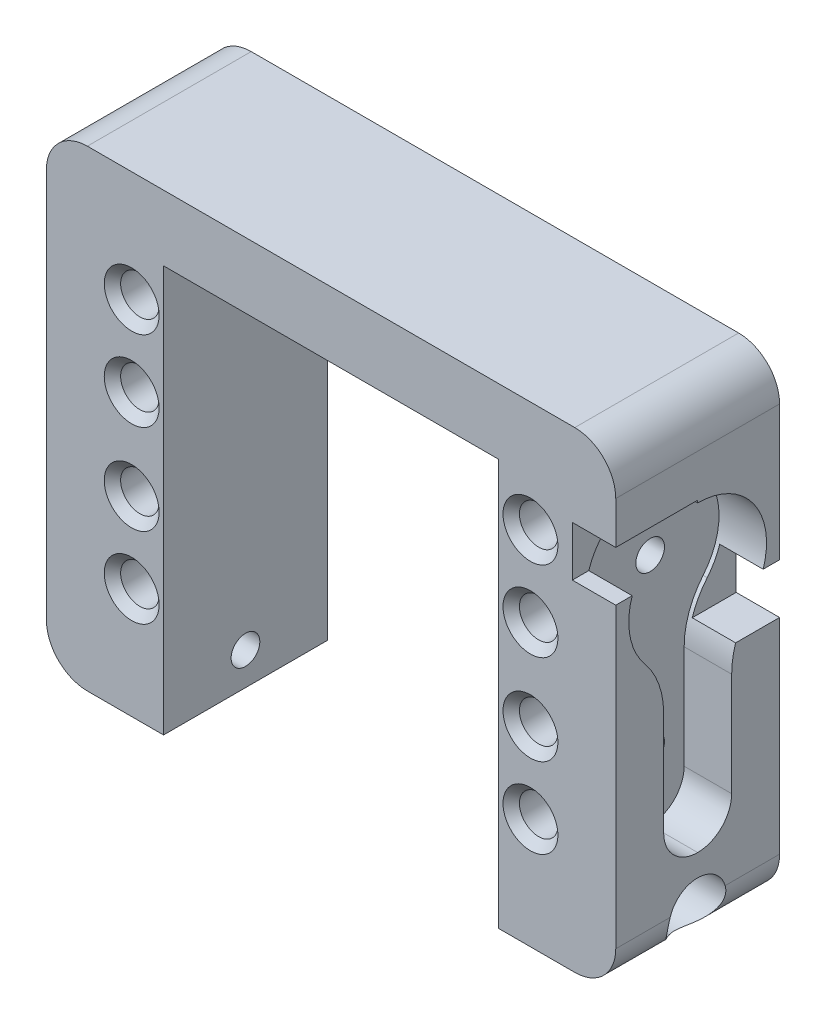
SolidWorks part; units mm, degrees
material "ABS"
ref_plane "Front Plane" through (0, 0, 0) normal (0, 0, 1) x (1, 0, 0)
ref_plane "Top Plane" through (0, 0, 0) normal (0, 1, 0) x (1, 0, 0)
ref_plane "Right Plane" through (0, 0, 0) normal (1, 0, 0) x (0, 0, -1)
sketch "Sketch1" plane through (0, 0, 0) normal (1, 0, 0) x (0, 0, -1)
  line L1 (-10, 10) -> (10, 10)
  line L2 (-10, 10) -> (-10, -10)
  line L3 (-10, -10) -> (10, -10)
  line L4 (10, 10) -> (10, -10)
  line L5 (-10, 10) -> (10, -10) construction
  line L6 (-10, -10) -> (10, 10) construction
  point P0 (0, 0)
  dimension "D1" = 20
  dimension "D2" = 20
extrude "Boss-Extrude1" add sketch "Sketch1" along normal blind 20
sketch "Sketch2" plane through (20, 0, 0) normal (1, 0, 0) x (0, 0, -1)
  line L1 (-10, 35) -> (10, 35)
  line L2 (-10, 35) -> (-10, -35)
  line L3 (-10, -35) -> (10, -35)
  line L4 (10, 35) -> (10, -35)
  line L5 (-10, 35) -> (10, -35) construction
  line L6 (-10, -35) -> (10, 35) construction
  point P0 (0, 0)
  dimension "D1" = 20
  dimension "D2" = 70
extrude "Boss-Extrude2" add sketch "Sketch2" along normal blind 10.3
sketch "Sketch4" plane through (30.3, 0, 0) normal (1, 0, 0) x (0, 0, -1)
  line L0 (0, 7.65) -> (0, 8.1702) construction
  line L1 (7.65, 7.65) -> (-7.65, 7.65) construction
  line L17 (4.15, -26.55) -> (-4.15, -26.55) construction
  line L18 (-7.65, 7.65) -> (7.65, 7.65) construction
  line L22 (-7.65, 7.65) -> (-7.65, -27.55) construction
  line L23 (-7.65, -27.55) -> (7.65, -27.55) construction
  line L24 (7.65, 7.65) -> (7.65, -27.55) construction
  line L25 (-7.65, 7.65) -> (7.65, -27.55) construction
  line L26 (-7.65, -27.55) -> (7.65, 7.65) construction
  line L27 (4.15, -26.55) -> (4.15, -28.55) construction
  line L28 (4.15, -28.55) -> (-4.15, -28.55) construction
  line L29 (-4.15, -26.55) -> (-4.15, -28.55) construction
  line L30 (4.15, -26.55) -> (-4.15, -28.55) construction
  line L31 (4.15, -28.55) -> (-4.15, -26.55) construction
  line L34 (4.15, -28.55) -> (-4.15, -28.55)
  line L35 (-4.15, -28.55) -> (-4.15, -7.3118)
  line L36 (4.15, -28.55) -> (4.15, -7.3118)
  arc A1 (4.15, -6.4265) -> (-4.15, -6.4265) centre (0, 0) ccw construction
  arc A2 (4.15, -7.3118) -> (-4.15, -7.3118) centre (0, 0) ccw
  point P1 (0, -27.55)
  point P7 (0, -13.75)
  point P10 (0, 7.65)
  point P14 (0, -9.95)
  dimension "D1" = 15.3
  dimension "D5" = 2
  dimension "D2" = 15.3
  dimension "D3" = 35.2
  dimension "D4" = 8.3
extrude "Cut-Extrude1" cut sketch "Sketch4" against normal blind 5.8
fillet "Fillet1" radius 4.15 2 edges at (27.4, -28.55, 4.15) (27.4, -28.55, -4.15)
fillet "Fillet2" radius 10 2 edges at (27.4, -7.3118, 4.15) (27.4, -7.3118, -4.15)
sketch "Sketch5" plane through (0, 0, 0) normal (-1, 0, 0) x (0, 0, 1)
  circle A0 centre (0, 0) radius 1.75
  dimension "D1" = 3.5
extrude "Cut-Extrude2" cut sketch "Sketch5" against normal through all
sketch "Sketch6" plane through (24.5, 0, 0) normal (1, 0, 0) x (0, 0, -1)
  line L0 (0, -19.35) -> (0, 0) construction
  line L1 (0, -25.65) -> (0, -23.15) construction
  line L2 (0, -23.15) -> (0, -21.85) construction
  line L3 (0, -21.85) -> (0, -19.35) construction
  line L5 (0, 0) -> (1.164, 0) construction
  line L6 (0, 0) -> (0, -9.35) construction
  line L7 (0, -9.35) -> (1.164, -9.35) construction
  line L8 (1.164, 0) -> (1.164, -9.35) construction
  line L9 (0, 0) -> (1.164, -9.35) construction
  line L10 (0, -9.35) -> (1.164, 0) construction
  circle A0 centre (0, -20.6) radius 1.75
  circle A1 centre (0, -9.35) radius 1.75 construction
  point P11 (0.582, -4.675)
  dimension "D5" = 3.5
  dimension "D6" = 9.35
  dimension "D7" = 3.5
  dimension "D1" = 19.35
  dimension "D2" = 2.5
  dimension "D3" = 1.3
  dimension "D4" = 2.5
extrude "Cut-Extrude3" cut sketch "Sketch6" against normal up to next
sketch "Sketch13" plane through (0, 0, 0) normal (-1, 0, 0) x (0, 0, 1)
  line L1 (-10, 10) -> (10, 10)
  line L2 (-10, 10) -> (-10, -10)
  line L3 (-10, -10) -> (10, -10)
  line L4 (10, 10) -> (10, -10)
extrude "Cut-Extrude9" cut sketch "Sketch13" against normal up to surface (20 mm away) up to face at (20, 22.5, 0)
sketch "Sketch29" plane through (30.3, 0, 0) normal (1, 0, 0) x (0, 0, -1)
  line L0 (0, 0) -> (0, 2.6) construction
  line L1 (15.1094, -8.7) -> (15.1094, -2.6)
  line L2 (0, 2.6) -> (-15.1094, 2.6)
  line L4 (0, 2.6) -> (0, 3.8)
  line L5 (0, 3.8) -> (0, 7.5)
  line L6 (0, 7.5) -> (0, 8.7)
  line L7 (0, 8.7) -> (-15.1094, 8.7)
  line L8 (-15.1094, 8.7) -> (-15.1094, 2.6)
  line L9 (0, -2.6) -> (15.1094, -2.6)
  line L10 (0, -2.6) -> (0, -3.8)
  line L11 (0, -3.8) -> (0, -7.5)
  line L12 (0, -7.5) -> (0, -8.7)
  line L13 (0, -8.7) -> (15.1094, -8.7)
  point P19 (0, 0)
  dimension "D1" = 2.6
  dimension "D2" = 1.2
  dimension "D3" = 3.7
  dimension "D4" = 1.2
  dimension "D5" = 2
extrude "Cut-Extrude18" cut sketch "Sketch29" against normal blind 5.3
sketch "Sketch32" plane through (30.3, 0, 0) normal (1, 0, 0) x (0, 0, -1)
  line L0 (0, -28.55) -> (0, -38.725) construction
  line L1 (10, -35) -> (10, -8.7) construction
  line L2 (-10, -35) -> (10, -35)
  line L3 (-10, -35) -> (-10, -38.725)
  line L4 (-10, -38.725) -> (10, -38.725)
  line L5 (10, -35) -> (10, -38.725)
  dimension "D1" = 10.175
extrude "Boss-Extrude3" add sketch "Sketch32" against normal up to surface (10.3 mm away) up to face at (20, 0, 0)
sketch "Sketch31" plane through (30.3, 0, 0) normal (1, 0, 0) x (0, 0, -1)
  line L2 (0, 8.7) -> (0, 18.875) construction
  line L3 (10, -2.6) -> (10, 35) construction
  line L4 (-10, 35) -> (10, 35)
  line L5 (-10, 35) -> (-10, 18.875)
  line L6 (-10, 18.875) -> (10, 18.875)
  line L7 (10, 35) -> (10, 18.875)
  dimension "D1" = 10.175
extrude "Cut-Extrude19" cut sketch "Sketch31" against normal through all
sketch "Sketch34" plane through (20, 0, 0) normal (-1, 0, 0) x (0, 0, 1)
  line L4 (10, -38.725) -> (10, 18.875)
  line L5 (10, 18.875) -> (-10, 18.875)
  line L6 (-10, 18.875) -> (-10, -38.725)
  line L7 (-10, -38.725) -> (10, -38.725)
  line L8 (10, -38.725) -> (10, 18.875)
  line L9 (10, 18.875) -> (-10, 18.875)
  line L10 (-10, 18.875) -> (-10, -38.725)
  line L11 (-10, -38.725) -> (10, -38.725)
  circle A0 centre (0, -20.6) radius 1.75 construction
  circle A1 centre (0, 0) radius 1.75 construction
  circle A2 centre (0, -20.6) radius 1.75
  circle A3 centre (0, 0) radius 1.75
  dimension "D1" = 0
extrude "Boss-Extrude5" add sketch "Sketch34" along normal blind 4
sketch "Sketch35" plane through (16, 0, 0) normal (-1, 0, 0) x (0, 0, 1)
  line L0 (10, -38.725) -> (10, 18.875) construction
  line L1 (-10, 18.875) -> (10, 18.875)
  line L2 (-10, 18.875) -> (-10, 10.875)
  line L3 (-10, 10.875) -> (10, 10.875)
  line L4 (10, 18.875) -> (10, 10.875)
  line L5 (0, 10.875) -> (0, -30.725) construction
  line L6 (-10, -38.725) -> (10, -38.725) construction
  line L7 (-10, -38.725) -> (-10, -30.725) construction
  line L8 (-10, -30.725) -> (10, -30.725) construction
  line L9 (10, -38.725) -> (10, -30.725) construction
  dimension "D1" = 41.6
extrude "Boss-Extrude6" add sketch "Sketch35" along normal blind 40.9
sketch "Sketch37" plane through (-24.9, 0, 0) normal (-1, 0, 0) x (0, 0, 1)
  line L1 (-10, 18.875) -> (10, 18.875)
  line L2 (-10, 18.875) -> (-10, -38.725)
  line L3 (-10, -38.725) -> (10, -38.725)
  line L4 (10, 18.875) -> (10, -38.725)
extrude "Boss-Extrude7" add sketch "Sketch37" along normal blind 14.3
sketch "Sketch38" plane through (0, 0, 10) normal (0, 0, 1) x (1, 0, 0)
  line L0 (-24.9, 10.875) -> (-24.9, -9.925) construction
  line L1 (-24.9, -9.925) -> (-24.9, -30.725) construction
  line L2 (-24.9, -38.725) -> (-24.9, 10.875) construction
  line L3 (-24.9, -9.925) -> (-39.2, -9.925) construction
  line L4 (-39.2, -38.725) -> (-39.2, 18.875) construction
  line L5 (-24.9, 0.475) -> (-28.79, 0.475) construction
  line L6 (-28.79, 0.475) -> (-28.79, 5.375) construction
  line L7 (-24.9, 10.875) -> (16, 10.875) construction
  line L8 (-4.45, 10.875) -> (-4.45, -38.725) construction
  line L9 (-24.9, -38.725) -> (-4.45, -38.725) construction
  circle A0 centre (-28.79, 5.375) radius 2.35
  circle A1 centre (-28.79, -4.425) radius 2.35
  circle A2 centre (-28.79, -25.225) radius 2.35
  circle A3 centre (-28.79, -15.425) radius 2.35
  circle A4 centre (19.89, 5.375) radius 2.35
  circle A5 centre (19.89, -4.425) radius 2.35
  circle A6 centre (19.89, -15.425) radius 2.35
  circle A7 centre (19.89, -25.225) radius 2.35
  dimension "D4" = 4.7
  dimension "D1" = 41.6
  dimension "D2" = 3.89
  dimension "D3" = 4.9
extrude "Cut-Extrude20" cut sketch "Sketch38" against normal blind 8
chamfer "Chamfer1" distance 1 angle 45 8 edges at (22.24, -25.225, 10) (17.54, -15.425, 10) (22.24, -4.425, 10) (17.54, 5.375, 10) (-26.44, 5.375, 10) (-26.44, -15.425, 10) (-31.14, -25.225, 10) (-31.14, -4.425, 10)
fillet "Fillet3" radius 5 2 edges at (30.3, 18.875, 0) (-39.2, 18.875, 0)
sketch "Sketch41" plane through (16, 0, 0) normal (-1, 0, 0) x (0, 0, 1)
  circle A0 centre (0, 0) radius 3.5
  circle A1 centre (0, -20.6) radius 3.5
  dimension "D1" = 7
  dimension "D2" = 7
extrude "Cut-Extrude23" cut sketch "Sketch41" against normal blind 2.5
sketch "Sketch45" plane through (30.3, 0, 0) normal (1, 0, 0) x (0, 0, -1)
  line L0 (0, -38.725) -> (0, -34.725) construction
  line L2 (-10, -38.725) -> (10, -38.725) construction
  line L3 (0, -34.725) -> (0, -28.55) construction
  circle A0 centre (0, -34.725) radius 1.75
  point P7 (0, 0)
  dimension "D1" = 3.5
  dimension "D2" = 4
extrude "Cut-Extrude27" cut sketch "Sketch45" against normal through all
sketch "Sketch46" plane through (-39.2, 0, 0) normal (-1, 0, 0) x (0, 0, 1)
  circle A0 centre (0, -34.725) radius 3.5
  dimension "D1" = 7
extrude "Cut-Extrude28" cut sketch "Sketch46" against normal blind 11
sketch "Sketch47" plane through (30.3, 0, 0) normal (1, 0, 0) x (0, 0, -1)
  circle A0 centre (0, -34.725) radius 3.5
  dimension "D1" = 7
extrude "Cut-Extrude29" cut sketch "Sketch47" against normal blind 11
fillet "Fillet5" radius 5 2 edges at (30.3, -38.725, 0) (-39.2, -38.725, 0)
